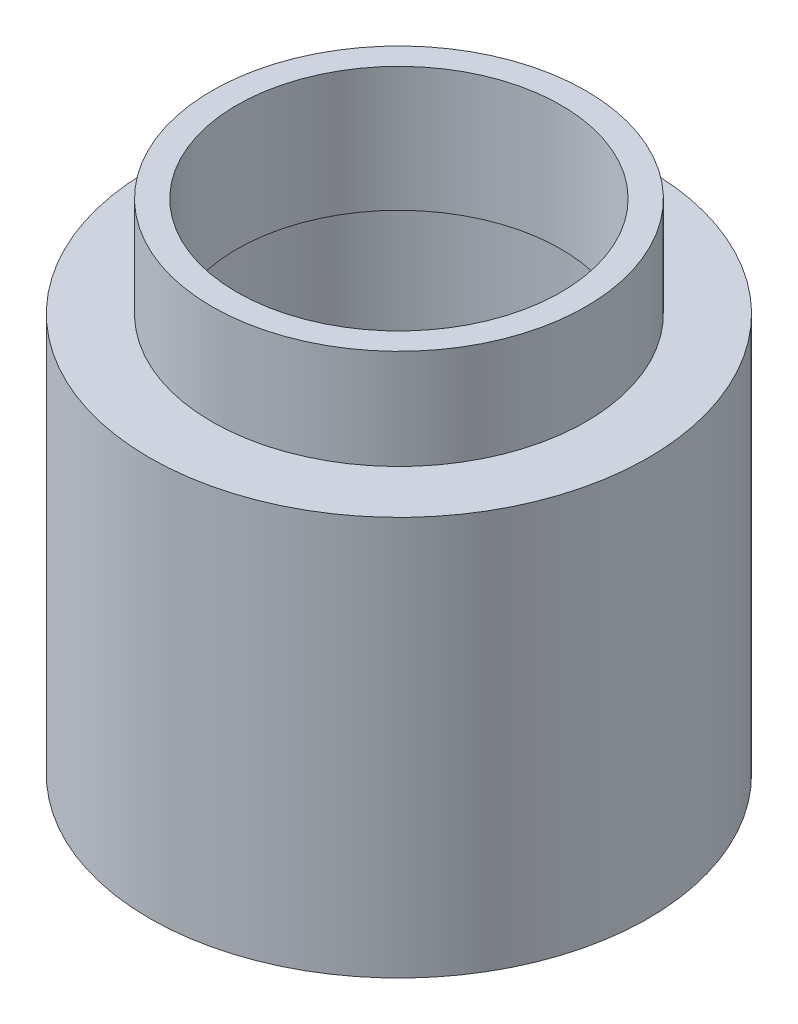
SolidWorks part; units mm, degrees
ref_plane "Front Plane" through (0, 0, 0) normal (0, 0, 1) x (1, 0, 0)
ref_plane "Top Plane" through (0, 0, 0) normal (0, 1, 0) x (1, 0, 0)
ref_plane "Right Plane" through (0, 0, 0) normal (1, 0, 0) x (0, 0, -1)
sketch "Sketch2" plane through (0, 0, 0) normal (0, 1, 0) x (1, 0, 0)
  line L0 (-24.4841, -6.7593) -> (24.4841, 6.7593) construction
  circle A0 centre (0, 0) radius 19.05
  circle A1 centre (0, 0) radius 25.4
  dimension "D1" = 38.1
  dimension "D2" = 50.8
extrude "Boss-Extrude1" add sketch "Sketch2" along normal blind 12.7 contours A0
extrude "Boss-Extrude3" add sketch "Sketch2<5>" against normal blind 38.1 separate body
sketch "Sketch2<5>" plane through (0, 0, 0) normal (0, 1, 0) x (1, 0, 0) same geometry as "Sketch2"
ref_axis "Axis1" through (0, -140.5896, 0) along (0, 1, 0)
shell "Shell2" thickness 2.54 removed face at (0, 0, 19.05) removed face at (0, 12.7, 19.05)
sketch "Sketch32" plane through (0, 0, 0) normal (1, 0, 0) x (0, 0, -1)
  line L0 (0, -38.1) -> (0, 0) construction
  line L1 (-25.4, -38.1) -> (25.4, -38.1) construction
  line L2 (-25.4, -19.05) -> (0, -19.05) construction
  line L3 (-25.4, 0) -> (-25.4, -38.1) construction
  line L4 (0, -19.05) -> (25.4, -19.05) construction
  line L5 (25.4, -38.1) -> (25.4, 0) construction
  circle A2 centre (0, -19.05) radius 9.525
  dimension "D1" = 19.05
extrude "Cut-Extrude1" cut sketch "Sketch32" against normal blind 50.8
extrude "Boss-Extrude4" add sketch "Sketch2<10>" along normal blind 2.54
sketch "Sketch2<10>" plane through (0, 0, 0) normal (0, 1, 0) x (1, 0, 0) same geometry as "Sketch2"
